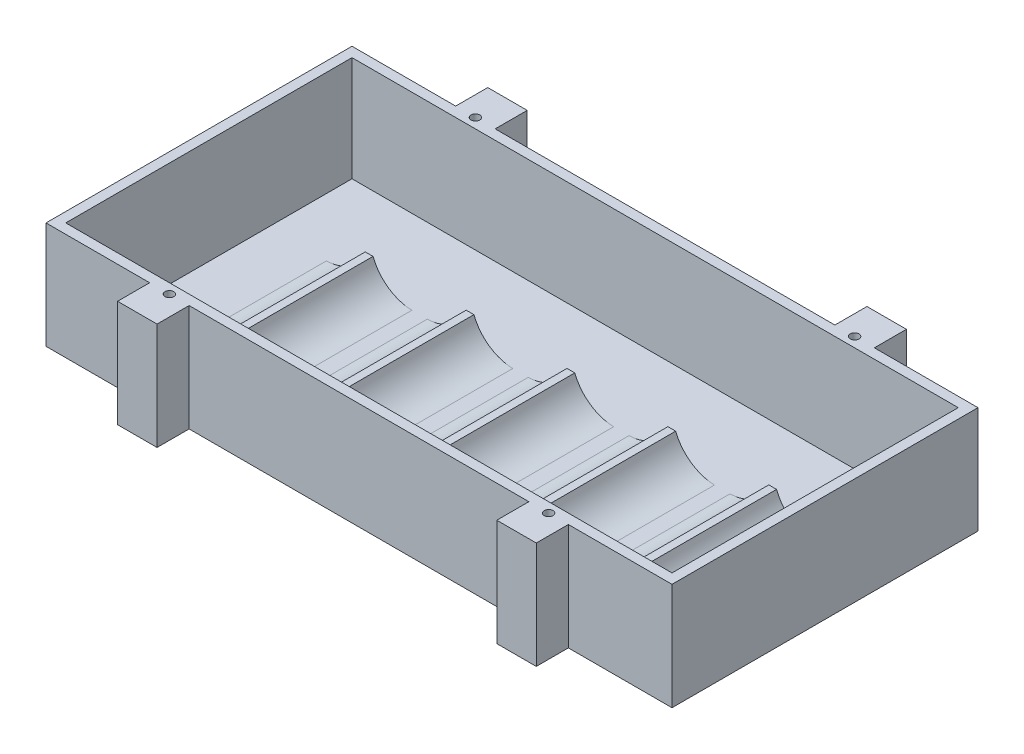
SolidWorks part; units mm, degrees
material "ABS"
ref_plane "Front Plane" through (0, 0, 0) normal (0, 0, 1) x (1, 0, 0)
ref_plane "Top Plane" through (0, 0, 0) normal (0, 1, 0) x (1, 0, 0)
ref_plane "Right Plane" through (0, 0, 0) normal (1, 0, 0) x (0, 0, -1)
sketch "Sketch1" plane through (0, 0, 0) normal (0, 1, 0) x (1, 0, 0)
  line L0 (2.54, -2.54) -> (2.54, -76.2)
  line L1 (0, 0) -> (161.08, 0)
  line L2 (0, 0) -> (0, -78.74)
  line L3 (0, -78.74) -> (161.08, -78.74)
  line L4 (161.08, 0) -> (161.08, -78.74)
  line L5 (2.54, -76.2) -> (158.54, -76.2)
  line L6 (158.54, -2.54) -> (158.54, -76.2)
  line L7 (2.54, -2.54) -> (158.54, -2.54)
  line L8 (0, 0) -> (0, 8.255)
  line L9 (0, 8.255) -> (161.08, 8.255)
  line L10 (161.08, 8.255) -> (161.08, 0)
  line L11 (0, -78.74) -> (0, -86.995)
  line L12 (0, -86.995) -> (161.08, -86.995)
  line L13 (161.08, -86.995) -> (161.08, -78.74)
  dimension "D1" = 73.66
  dimension "D2" = 156
  dimension "D4" = 10.795
  dimension "D5" = 95.25
  dimension "D3" = 2.54
extrude "Boss-Extrude1" add sketch "Sketch1" against normal blind 0.508 contours L2 L3 L4 L1
extrude "Boss-Extrude2" add sketch "Sketch1<3>" along normal blind 27 contours L10 L9 L8 L1 | L12 L13 L3 L11 | L4 L1 L2 L3 L0 L7 L6 L5 region at (80.54, 0, -4.1275) region at (80.54, 0, 1.793) region at (80.54, 0, 82.8675)
sketch "Sketch1<3>" plane through (0, 0, 0) normal (0, 1, 0) x (1, 0, 0) same geometry as "Sketch1"
sketch "Sketch2" plane through (0, 0, 0) normal (0, 1, 0) x (-1, 0, 0)
  line L0 (-28.54, 0) -> (-28.54, 78.74) construction
  line L1 (-2.54, 2.54) -> (-2.54, 76.2) construction
  line L2 (-17.54, 0) -> (-17.54, 78.74) construction
  line L9 (0, 0) -> (-161.08, 0) construction
  line L10 (0, 78.74) -> (-161.08, 78.74) construction
  dimension "D1" = 26
  dimension "D2" = 15
sketch "Sketch5" plane through (0, 0, 2.54) normal (0, 0, 1) x (1, 0, 0)
  line L0 (28.54, 0) -> (28.54, 7) construction
  line L1 (29.54, 7) -> (27.54, 7)
  line L2 (0, 0) -> (161.08, 0) construction
  line L3 (17.54, 0) -> (39.54, 0)
  line L4 (55.4988, 7) -> (53.4988, 7)
  line L5 (43.4988, 0) -> (65.4988, 0)
  line L6 (54.4988, 0) -> (54.4988, 7) construction
  line L7 (81.4576, 7) -> (79.4576, 7)
  line L8 (69.4576, 0) -> (91.4576, 0)
  line L9 (80.4576, 0) -> (80.4576, 7) construction
  line L10 (107.4164, 7) -> (105.4164, 7)
  line L11 (95.4164, 0) -> (117.4164, 0)
  line L12 (106.4164, 0) -> (106.4164, 7) construction
  line L13 (133.3752, 7) -> (131.3752, 7)
  line L14 (121.3752, 0) -> (143.3752, 0)
  line L15 (132.3752, 0) -> (132.3752, 7) construction
  line L31 (159.334, 7) -> (157.334, 7) [skipped]
  line L32 (147.334, 0) -> (169.334, 0) [skipped]
  line L33 (158.334, 0) -> (158.334, 7) construction
  line L37 (170.06, 7) -> (168.06, 7) [skipped]
  line L38 (158.06, 0) -> (180.06, 0) [skipped]
  line L39 (169.06, 0) -> (169.06, 7) construction
  line L40 (145.64, 0) -> (145.64, 7) construction
  line L41 (134.64, 0) -> (156.64, 0) [skipped]
  line L42 (146.64, 7) -> (144.64, 7) [skipped]
  line L43 (122.22, 0) -> (122.22, 7) construction
  line L44 (111.22, 0) -> (133.22, 0) [skipped]
  line L45 (123.22, 7) -> (121.22, 7) [skipped]
  line L46 (98.8, 0) -> (98.8, 7) construction
  line L47 (87.8, 0) -> (109.8, 0) [skipped]
  line L48 (99.8, 7) -> (97.8, 7) [skipped]
  line L49 (75.38, 0) -> (75.38, 7) construction
  line L50 (64.38, 0) -> (86.38, 0) [skipped]
  line L51 (76.38, 7) -> (74.38, 7) [skipped]
  line L52 (51.96, 0) -> (51.96, 7) construction
  line L53 (40.96, 0) -> (62.96, 0) [skipped]
  line L54 (52.96, 7) -> (50.96, 7) [skipped]
  arc A0 (17.54, 0) -> (27.54, 7) centre (17.292, 10.9972) ccw
  arc A1 (39.54, 0) -> (29.54, 7) centre (39.788, 10.9972) cw
  arc A2 (65.4988, 0) -> (55.4988, 7) centre (65.7468, 10.9972) cw
  arc A3 (43.4988, 0) -> (53.4988, 7) centre (43.2508, 10.9972) ccw
  arc A4 (91.4576, 0) -> (81.4576, 7) centre (91.7056, 10.9972) cw
  arc A5 (69.4576, 0) -> (79.4576, 7) centre (69.2096, 10.9972) ccw
  arc A6 (117.4164, 0) -> (107.4164, 7) centre (117.6644, 10.9972) cw
  arc A7 (95.4164, 0) -> (105.4164, 7) centre (95.1684, 10.9972) ccw
  arc A8 (143.3752, 0) -> (133.3752, 7) centre (143.6232, 10.9972) cw
  arc A9 (121.3752, 0) -> (131.3752, 7) centre (121.1272, 10.9972) ccw
  arc A20 (169.334, 0) -> (159.334, 7) centre (169.582, 10.9972) cw [skipped]
  arc A21 (147.334, 0) -> (157.334, 7) centre (147.086, 10.9972) ccw [skipped]
  arc A24 (180.06, 0) -> (170.06, 7) centre (180.308, 10.9972) cw [skipped]
  arc A25 (158.06, 0) -> (168.06, 7) centre (157.812, 10.9972) ccw [skipped]
  arc A26 (134.64, 0) -> (144.64, 7) centre (134.392, 10.9972) ccw [skipped]
  arc A27 (156.64, 0) -> (146.64, 7) centre (156.888, 10.9972) cw [skipped]
  arc A28 (111.22, 0) -> (121.22, 7) centre (110.972, 10.9972) ccw [skipped]
  arc A29 (133.22, 0) -> (123.22, 7) centre (133.468, 10.9972) cw [skipped]
  arc A30 (87.8, 0) -> (97.8, 7) centre (87.552, 10.9972) ccw [skipped]
  arc A31 (109.8, 0) -> (99.8, 7) centre (110.048, 10.9972) cw [skipped]
  arc A32 (64.38, 0) -> (74.38, 7) centre (64.132, 10.9972) ccw [skipped]
  arc A33 (86.38, 0) -> (76.38, 7) centre (86.628, 10.9972) cw [skipped]
  arc A34 (62.96, 0) -> (52.96, 7) centre (63.208, 10.9972) cw [skipped]
  arc A35 (40.96, 0) -> (50.96, 7) centre (40.712, 10.9972) ccw [skipped]
  dimension "D2" = 11
  dimension "D1" = 1
  dimension "D3" = 7
  dimension "D4" = 6
  dimension "D5" = 5
extrude "Boss-Extrude3" add sketch "Sketch5" along normal blind 32.5 from offset 21.59
extrude "Boss-Extrude4" add sketch "Sketch1<4>" against normal up to surface (0.508 mm away) contours L10 L9 L8 L1 | L12 L13 L3 L11 region at (80.54, 0, -4.1275) region at (80.54, 0, 82.8675) up to face at (80.54, -0.508, 39.37)
sketch "Sketch1<4>" plane through (0, 0, 0) normal (0, 1, 0) x (1, 0, 0) same geometry as "Sketch1"
sketch "Sketch6" plane through (0, 27, 0) normal (0, 1, 0) x (1, 0, 0)
  line L0 (0, 0) -> (161.08, 0) construction
  line L1 (161.08, 8.255) -> (161.08, -86.995) construction
  line L2 (0, -86.995) -> (0, 8.255) construction
  line L3 (0, -39.37) -> (14.6137, -39.37) construction
  point P5 (31.75, 0)
  point P6 (129.33, 0)
  point P9 (129.33, -78.74)
  point P10 (31.75, -78.74)
  dimension "D1" = 31.75
  dimension "D2" = 31.75
hole_wizard "#4-40 Tapped Hole2" positions "Sketch10" profile "Sketch9" tap size "#4-40" standard "Ansi Inch"
sketch "Sketch10" plane through (0, 27, 0) normal (0, 1, 0) x (-1, 0, 0)
  point P0 (-31.75, 0)
  point P1 (-129.33, 0)
  point P8 (-31.75, 78.74)
  point P11 (-129.33, 78.74)
sketch "Sketch9" plane through (31.75, 27, 0) normal (1, 0, 0) x (0, 0, 1)
  line L0 (0, 0) -> (0, 8.2992)
  line L1 (0, 8.2992) -> (1.1303, 7.62)
  line L2 (1.1303, 7.62) -> (1.1303, 0)
  line L5 (1.1303, 0) -> (0, 0)
  line L10 (0, 8.2992) -> (-1.1303, 7.62) construction
  line L11 (0, -6.35) -> (0, 107.95) construction
  dimension "Tap Drill Dia." = 2.2606
  dimension "Tap Drill Depth" = 7.62
  dimension "Drill Angle" = 118
cosmetic thread "Hole Thread2" parameters "D1"=5.588, "D2"=2.8448
cosmetic thread "Hole Thread3" parameters "D1"=5.588, "D2"=2.8448
cosmetic thread "Hole Thread4" parameters "D1"=5.588, "D2"=2.8448
cosmetic thread "Hole Thread5" parameters "D1"=5.588, "D2"=2.8448
sketch "midpoint" plane through (0, 27, 0) normal (0, 1, 0) x (1, 0, 0)
  line L0 (80.54, 8.255) -> (80.54, -86.995) construction
  line L1 (0, 8.255) -> (161.08, 8.255) construction
  line L2 (0, -86.995) -> (161.08, -86.995) construction
sketch "Sketch11" plane through (0, 27, 0) normal (0, 1, 0) x (1, 0, 0)
  line L0 (0, 8.255) -> (161.08, 8.255) construction
  line L1 (36.83, 8.255) -> (124.25, 8.255)
  line L2 (36.83, 8.255) -> (36.83, 0)
  line L3 (36.83, 0) -> (124.25, 0)
  line L4 (124.25, 8.255) -> (124.25, 0)
  line L5 (2.54, -2.54) -> (158.54, -2.54) construction
  line L6 (0, -39.37) -> (15.7032, -39.37) construction
  line L7 (0, -86.995) -> (0, 8.255) construction
  line L8 (124.25, -86.995) -> (124.25, -78.74)
  line L9 (36.83, -86.995) -> (124.25, -86.995)
  line L10 (36.83, -78.74) -> (124.25, -78.74)
  line L11 (36.83, -86.995) -> (36.83, -78.74)
  line L12 (80.54, 8.255) -> (80.54, -12.9141) construction
  line L13 (0, 8.255) -> (26.67, 8.255)
  line L14 (0, 8.255) -> (0, 0)
  line L15 (0, 0) -> (26.67, 0)
  line L16 (26.67, 8.255) -> (26.67, 0)
  line L17 (161.08, 8.255) -> (161.08, 0)
  line L18 (161.08, 8.255) -> (134.41, 8.255)
  line L19 (134.41, 8.255) -> (134.41, 0)
  line L20 (161.08, 0) -> (134.41, 0)
  line L21 (161.08, -86.995) -> (161.08, -78.74)
  line L22 (161.08, -86.995) -> (134.41, -86.995)
  line L23 (134.41, -86.995) -> (134.41, -78.74)
  line L24 (161.08, -78.74) -> (134.41, -78.74)
  line L25 (0, -86.995) -> (0, -78.74)
  line L26 (0, -86.995) -> (26.67, -86.995)
  line L27 (26.67, -86.995) -> (26.67, -78.74)
  line L28 (0, -78.74) -> (26.67, -78.74)
  dimension "D1" = 5.08
  dimension "D2" = 5.08
  dimension "D3" = 2.54
  dimension "D4" = 2.54
  dimension "D5" = 5.08
extrude "Cut-Extrude1" cut sketch "Sketch11" against normal through all
